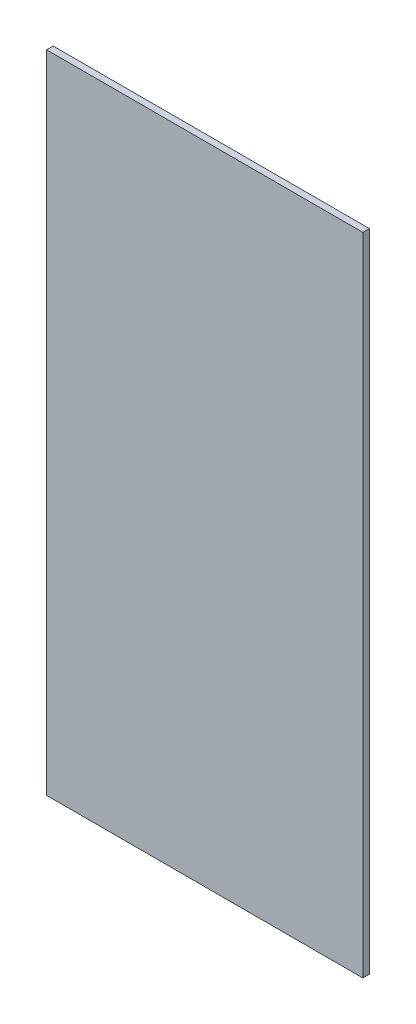
SolidWorks part; units mm, degrees
ref_plane "Front Plane" through (0, 0, 0) normal (0, 0, 1) x (1, 0, 0)
ref_plane "Top Plane" through (0, 0, 0) normal (0, 1, 0) x (1, 0, 0)
ref_plane "Right Plane" through (0, 0, 0) normal (1, 0, 0) x (0, 0, -1)
sketch "Sketch1" plane through (0, 0, 0) normal (0, 0, 1) x (1, 0, 0)
  line L1 (-438.9437, 896.1438) -> (438.9437, 896.1438)
  line L2 (-438.9437, 896.1438) -> (-438.9437, -896.1437)
  line L3 (-438.9437, -896.1437) -> (438.9438, -896.1437)
  line L4 (438.9437, 896.1438) -> (438.9438, -896.1437)
  line L5 (-438.9437, 896.1438) -> (438.9438, -896.1437) construction
  line L6 (-438.9437, -896.1437) -> (438.9437, 896.1438) construction
  point P0 (0, 0)
  dimension "D1" = 1792.2875
  dimension "D2" = 877.8875
extrude "Boss-Extrude1" add sketch "Sketch1" along normal blind 18.2562
